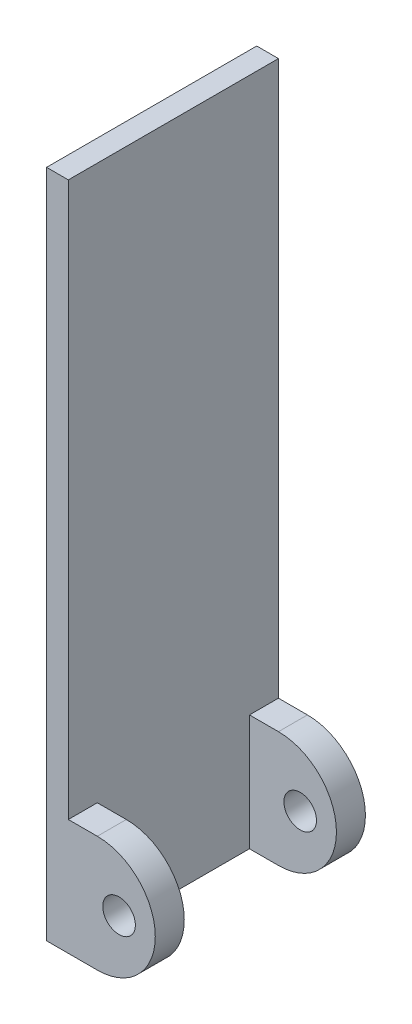
SolidWorks part; units mm, degrees
ref_plane "Front Plane" through (0, 0, 0) normal (0, 0, 1) x (1, 0, 0)
ref_plane "Top Plane" through (0, 0, 0) normal (0, 1, 0) x (1, 0, 0)
ref_plane "Right Plane" through (0, 0, 0) normal (1, 0, 0) x (0, 0, -1)
sketch "Sketch1" plane through (0, 0, 0) normal (0, 0, 1) x (1, 0, 0)
  line L1 (1.5, 46.223) -> (-1.5, 46.223)
  line L2 (1.5, 46.223) -> (1.5, -46.223)
  line L3 (1.5, -46.223) -> (-1.5, -46.223)
  line L4 (-1.5, 46.223) -> (-1.5, -46.223)
  line L5 (1.5, 46.223) -> (-1.5, -46.223) construction
  line L6 (1.5, -46.223) -> (-1.5, 46.223) construction
  point P0 (0, 0)
  dimension "D1" = 3
  dimension "D2" = 92.446
extrude "Boss-Extrude1" add sketch "Sketch1" along normal blind 29
sketch "Sketch2" plane through (0, 0, 29) normal (0, 0, 1) x (1, 0, 0)
  line L0 (-1.5, 46.223) -> (-1.5, -46.223) construction
  line L1 (-1.5, -46.223) -> (1.5, -46.223) construction
  line L2 (8.5, 38.223) -> (8.5, -38.223) construction
  line L4 (1.5, 46.223) -> (13.5, 46.223)
  line L5 (1.5, 46.223) -> (1.5, 30.223)
  line L6 (1.5, 30.223) -> (13.5, 30.223)
  line L7 (13.5, 46.223) -> (13.5, 30.223)
  line L8 (1.5, -46.223) -> (13.5, -46.223)
  line L9 (1.5, -46.223) -> (1.5, -30.223)
  line L10 (1.5, -30.223) -> (13.5, -30.223)
  line L11 (13.5, -46.223) -> (13.5, -30.223)
  line L12 (1.5, 46.223) -> (-1.5, 46.223) construction
  circle A0 centre (8.5, 38.223) radius 2.25
  circle A1 centre (8.5, -38.223) radius 2.25
  line M11 (1.5, -46.223) -> (1.5, 46.223)
  dimension "D3" = 4.5
  dimension "D1" = 8
  dimension "D2" = 10
  dimension "D4" = 8
  dimension "D5" = 16
  dimension "D6" = 12
extrude "Boss-Extrude2" add sketch "Sketch2" against normal blind 4 contours L8 L11 L10 A1 M11 region at (7.5, -30.423, 29)
fillet "Fillet1" [suppressed] type full round
fillet "Fillet2" 2 edges at (13.5, -30.223, 27) (13.5, -46.223, 27) type full round first side face at (7.5, -30.223, 27) second side face at (4.5, -46.223, 18) middle face at (13.5, -38.223, 27)
ref_plane "Plane1" through (0, 0, 14.5) normal (0, 0, 1) x (1, 0, 0)
ref_plane "Plane2" through (0, 0, 15) normal (0, 0, 1) x (1, 0, 0)
sketch "Sketch3" plane through (0, 0, 15) normal (0, 0, 1) x (1, 0, 0)
  line L0 (1.5, -46.223) -> (1.5, 46.223) construction
  line L1 (1.5, 37.731) -> (9.5, 37.731)
  line L2 (1.5, 37.731) -> (1.5, 45.731)
  line L3 (1.5, 45.731) -> (9.5, 45.731)
  line L4 (9.5, 37.731) -> (9.5, 45.731)
  circle A0 centre (7, 41.731) radius 1.5
  dimension "D3" = 3
  dimension "D1" = 8
  dimension "D2" = 8
  dimension "D4" = 2.5
  dimension "D5" = 4
  dimension "D6" = 0.492
extrude "Boss-Extrude4" [suppressed] add sketch "Sketch3" along normal blind 4
mirror "Mirror2" about plane through (0, 0, 14.5) normal (0, 0, 1) of "Fillet2", "Boss-Extrude2"
